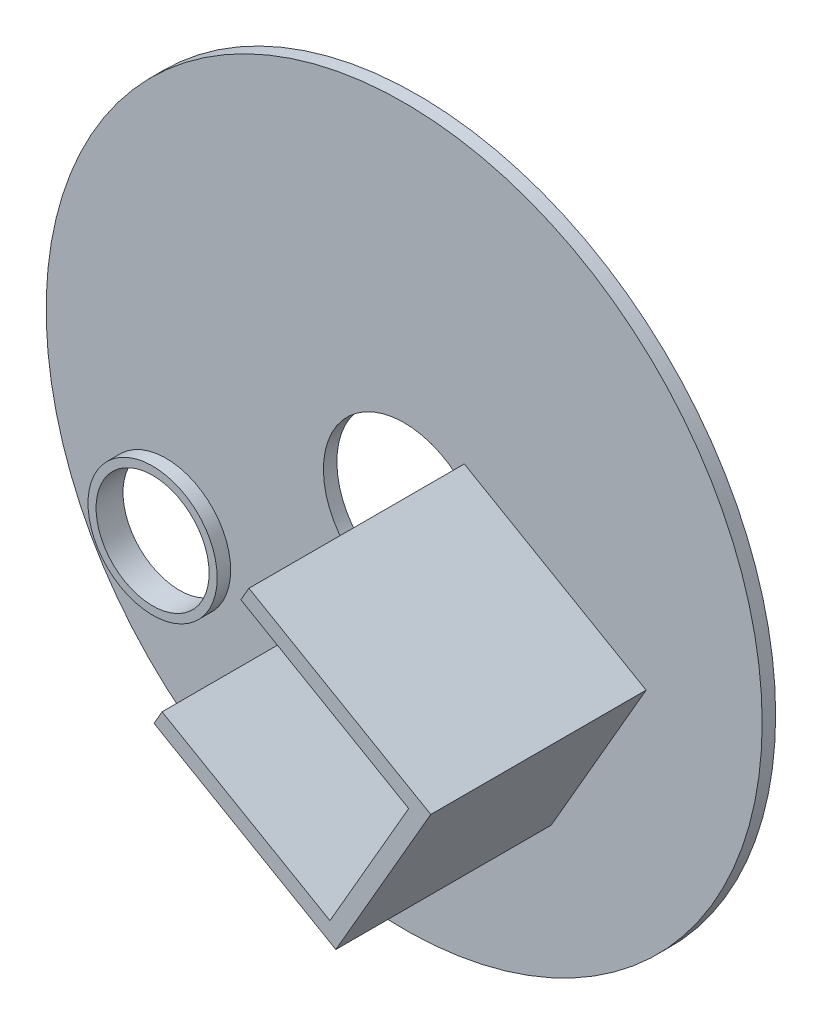
SolidWorks part; units mm, degrees
ref_plane "Front Plane" through (0, 0, 0) normal (0, 0, 1) x (1, 0, 0)
ref_plane "Top Plane" through (0, 0, 0) normal (0, 1, 0) x (1, 0, 0)
ref_plane "Right Plane" through (0, 0, 0) normal (1, 0, 0) x (0, 0, -1)
sketch "Sketch1" plane through (0, 0, 0) normal (0, 0, 1) x (1, 0, 0)
  circle A1 centre (0, 0) radius 66.5
  circle A2 centre (0, 0) radius 15
extrude "Boss-Extrude1" add sketch "Sketch1" along normal blind 2.5
sketch "Sketch3" plane through (-7.3033, 6.6987, 2.5) normal (0, 0, 1) x (1, 0, 0)
  circle A3 centre (-36.9235, -31.5273) radius 10.5
  circle A4 centre (-36.9235, -31.5273) radius 12
extrude "Cut-Extrude1" cut sketch "Sketch3" against normal blind 13.5 contours A3
extrude "Boss-Extrude2" add sketch "Sketch3<3>" along normal blind 2.5
sketch "Sketch3<3>" plane through (-7.3033, 6.6987, 2.5) normal (0, 0, 1) x (1, 0, 0) same geometry as "Sketch3"
sketch "Sketch6" plane through (0, 0, 0) normal (0, 0, 1) x (1, 0, 0)
  line L0 (0, 0) -> (0, 66.5)
  circle A0 centre (0, 0) radius 66.5 construction
sketch "Sketch13" plane through (0, 0, 0) normal (0, 0, 1) x (1, 0, 0)
  line L0 (33.51, -19.347) -> (40.8449, -6.6426)
  line L1 (33.51, -19.347) -> (26.21, -31.991)
  line L2 (26.21, -31.991) -> (-4.967, -13.991)
  line L3 (40.8449, -6.6426) -> (9.6679, 11.3574)
extrude "Extrude-Thin1" add sketch "Sketch13" along normal blind 42.5 thin thin type one direction wall 2.9988
